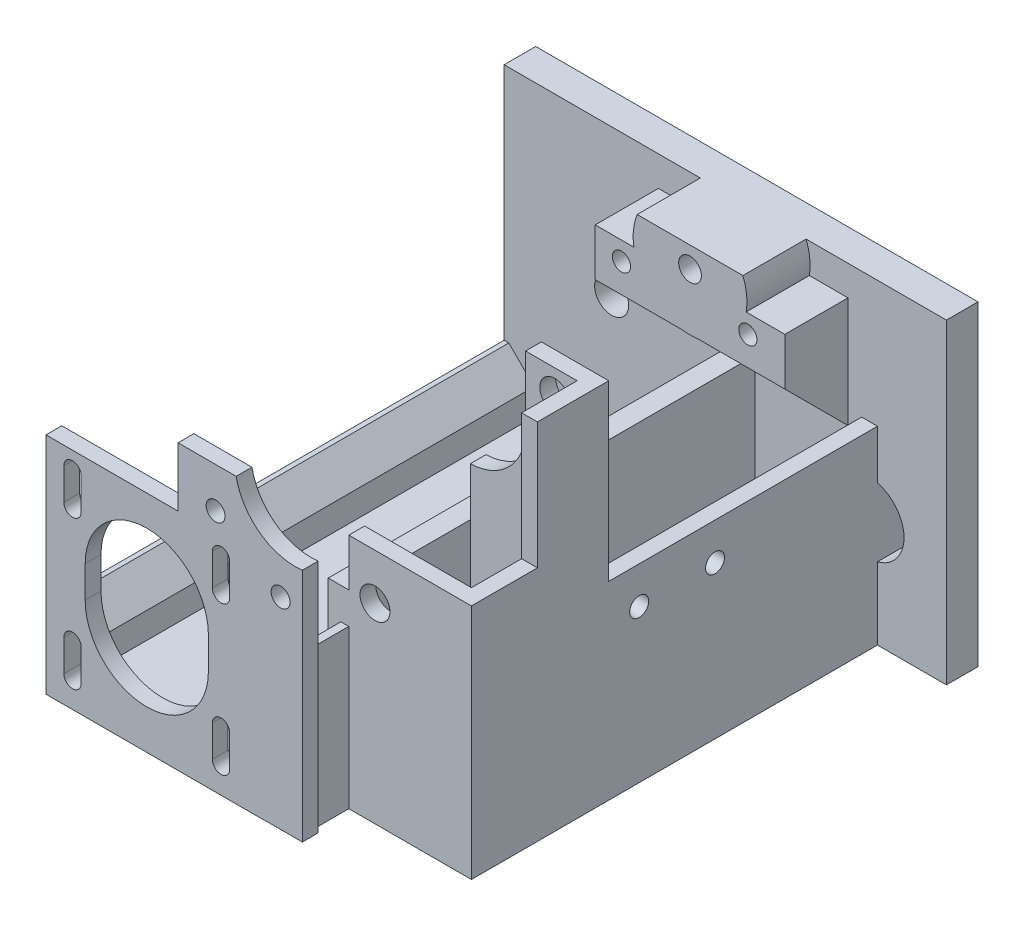
SolidWorks part; units mm, degrees
material "ABS"
ref_plane "Front Plane" through (0, 0, 0) normal (0, 0, 1) x (1, 0, 0)
ref_plane "Top Plane" through (0, 0, 0) normal (0, 1, 0) x (1, 0, 0)
ref_plane "Right Plane" through (0, 0, 0) normal (1, 0, 0) x (0, 0, -1)
sketch "Sketch1" plane through (0, 0, 0) normal (0, 0, 1) x (1, 0, 0)
  line L1 (-65.5446, 32.6733) -> (74.4554, 32.6733)
  line L2 (-65.5446, 32.6733) -> (-65.5446, -67.3267)
  line L3 (-65.5446, -67.3267) -> (74.4554, -67.3267)
  line L4 (74.4554, 32.6733) -> (74.4554, -67.3267)
  dimension "D1" = 100
  dimension "D2" = 140
extrude "Boss-Extrude1" add sketch "Sketch1" along normal blind 10
sketch "Sketch2" plane through (0, 0, 10) normal (0, 0, 1) x (1, 0, 0)
  line L0 (-65.5446, -67.3267) -> (-65.5446, -42.849)
  line L3 (-65.5446, -67.3267) -> (7.3151, -67.3267)
  line L5 (-65.5446, -67.3267) -> (74.4554, -67.3267) construction
  line L8 (-65.5446, 32.6733) -> (-65.5446, -67.3267) construction
  line L9 (-65.5446, -42.849) -> (-56.0483, -42.849)
  line L10 (-56.0483, -42.849) -> (-56.0483, -59.0904)
  line L11 (-56.0483, -59.0904) -> (7.3151, -59.0904)
  line L12 (7.3151, -59.0904) -> (7.3151, -7.3423)
  line L13 (7.3151, -7.3423) -> (13.8255, -7.3423)
  line L14 (13.8255, -7.3423) -> (13.8255, -67.3267)
  line L15 (13.8255, -67.3267) -> (7.3151, -67.3267)
extrude "Boss-Extrude2" add sketch "Sketch2" along normal blind 140
sketch "Sketch3" plane through (0, 0, 10) normal (0, 0, 1) x (1, 0, 0)
  line L1 (-16.6941, 23.1955) -> (43.3059, 23.1955)
  line L2 (-16.6941, 23.1955) -> (-16.6941, 8.1955)
  line L3 (-16.6941, 8.1955) -> (43.3059, 8.1955)
  line L4 (43.3059, 23.1955) -> (43.3059, 8.1955)
  dimension "D1" = 15
  dimension "D2" = 60
extrude "Boss-Extrude3" add sketch "Sketch3" along normal blind 20
sketch "Sketch4" plane through (0, 0, 10) normal (0, 0, 1) x (1, 0, 0)
  line L0 (43.3059, 8.1955) -> (43.3059, 23.1955) construction
  circle A0 centre (13.3059, 26.0432) radius 18
  dimension "D1" = 36
  dimension "D2" = 30
extrude "Boss-Extrude4" add sketch "Sketch4" along normal blind 20
sketch "Sketch6" plane through (0, 0, 30) normal (0, 0, 1) x (1, 0, 0)
  circle A0 centre (13.3059, 26.0432) radius 3.5973
  arc A1 (31.0792, 23.1955) -> (-4.4674, 23.1955) centre (13.3059, 26.0432) ccw construction
extrude "Cut-Extrude2" cut sketch "Sketch6" against normal blind 100
sketch "Sketch5" plane through (0, 0, 30) normal (0, 0, 1) x (1, 0, 0)
  line L0 (74.4554, 32.6733) -> (30.0404, 32.6733) construction
  line L1 (-13.303, 47.4) -> (34.4273, 47.4)
  line L2 (-13.303, 47.4) -> (-13.303, 32.6733)
  line L3 (-13.303, 32.6733) -> (34.4273, 32.6733)
  line L4 (34.4273, 47.4) -> (34.4273, 32.6733)
extrude "Cut-Extrude1" cut sketch "Sketch5" against normal blind 20
sketch "Sketch7" plane through (0, 0, 30) normal (0, 0, 1) x (1, 0, 0)
  circle A0 centre (-8.3949, 17.2978) radius 2.8779
extrude "Cut-Extrude3" cut sketch "Sketch7" against normal blind 100
pattern_linear "LPattern1" count 2 spacing 40 along (1, 0, 0) of "Cut-Extrude3"
sketch "Sketch9" plane through (0, 0, 150) normal (0, 0, 1) x (1, 0, 0)
  line L0 (-65.5446, 32.6733) -> (-65.5446, -42.849) construction
  line L1 (4.1877, 3.7072) -> (-65.5446, 3.7072)
  line L2 (4.1877, 3.7072) -> (4.1877, -67.3896)
  line L3 (4.1877, -67.3896) -> (-65.5446, -67.3896)
  line L4 (-65.5446, 3.7072) -> (-65.5446, -67.3896)
extrude "Boss-Extrude5" add sketch "Sketch9" along normal blind 5
chamfer "Chamfer1" distance 20 angle 45 2 edges at (29.4741, 8.1955, 10) (-2.8623, 8.1955, 10)
sketch "Sketch11" plane through (0, 0, 155) normal (0, 0, 1) x (1, 0, 0)
  line L0 (13.8255, -67.3267) -> (74.4554, -67.3267) construction
  line L1 (-23.7439, 22.4423) -> (15.6103, 22.4423)
  line L2 (-23.7439, 22.4423) -> (-23.7439, -67.3267)
  line L3 (-23.7439, -67.3267) -> (15.6103, -67.3267)
  line L4 (15.6103, 22.4423) -> (15.6103, -67.3267)
extrude "Boss-Extrude6" add sketch "Sketch11" against normal blind 5
sketch "Sketch12" plane through (0, 0, 155) normal (0, 0, 1) x (1, 0, 0)
  circle A0 centre (13.3059, 26.0432) radius 19
extrude "Cut-Extrude5" cut sketch "Sketch12" against normal blind 10
sketch "Sketch13" plane through (0, 0, 155) normal (0, 0, 1) x (1, 0, 0)
  circle A0 centre (-11.8599, 9.7129) radius 3
  circle A1 centre (8.7091, -3.6025) radius 3
  circle A2 centre (13.3059, 26.0432) radius 30 construction
  dimension "D1" = 6
  dimension "D2" = 6
extrude "Cut-Extrude6" cut sketch "Sketch13" against normal blind 10
fillet "Fillet2" radius 10 rebuild error yes
chamfer "Chamfer2" distance 8 angle 45 1 edges at (-56.0483, -42.849, 80)
sketch "Sketch14" plane through (0, 0, 10) normal (0, 0, 1) x (1, 0, 0)
  circle A0 centre (-31.5077, -13.6101) radius 5.3914
  circle A1 centre (49.8779, -33.6888) radius 11.1548
extrude "Cut-Extrude7" cut sketch "Sketch14" against normal blind 10
sketch "Sketch15" plane through (0, -67.3267, 0) normal (0, -1, 0) x (1, 0, 0)
  line L1 (4.5956, 95.0738) -> (52.6384, 95.0738)
  line L2 (4.5956, 95.0738) -> (4.5956, 138.5253)
  line L3 (4.5956, 138.5253) -> (52.6384, 138.5253)
  line L4 (52.6384, 95.0738) -> (52.6384, 138.5253)
extrude "Boss-Extrude7" add sketch "Sketch15" against normal blind 5
sketch "Sketch16" plane through (0, -62.3267, 0) normal (0, 1, 0) x (1, 0, 0)
  line L8 (13.8255, -133.5253) -> (13.8255, -138.5253)
  line L9 (13.8255, -138.5253) -> (13.8255, -95.0738) construction
  line L10 (13.8255, -138.5253) -> (52.6384, -138.5253)
  line L11 (52.6384, -138.5253) -> (52.6384, -116.7995)
  line L12 (52.6384, -95.0738) -> (52.6384, -138.5253) construction
  line L13 (52.6384, -116.7995) -> (47.6384, -116.7995)
  line L14 (47.6384, -116.7995) -> (47.6384, -133.5253)
  line L15 (47.6384, -133.5253) -> (13.8255, -133.5253)
  dimension "D1" = 5
  dimension "D2" = 5
extrude "Boss-Extrude8" add sketch "Sketch16" along normal blind 70
sketch "Sketch17" plane through (0, 7.6733, 0) normal (0, 1, 0) x (1, 0, 0)
  line L1 (28.8586, -179.0031) -> (38.4745, -179.0031)
  line L2 (28.8586, -179.0031) -> (28.8586, -197.9959)
  line L3 (28.8586, -197.9959) -> (38.4745, -197.9959)
  line L4 (38.4745, -179.0031) -> (38.4745, -197.9959)
extrude "Cut-Extrude8" cut sketch "Sketch17" against normal blind 20 rebuild error yes
sketch "Sketch18" plane through (0, 0, 138.5253) normal (0, 0, 1) x (1, 0, 0)
  circle A0 centre (22.1124, -6.8448) radius 4.75
  dimension "D1" = 9.5
extrude "Cut-Extrude9" cut sketch "Sketch18" against normal blind 20
sketch "Sketch19" plane through (0, -62.3267, 0) normal (0, 1, 0) x (1, 0, 0)
  line L0 (13.8199, -95.0738) -> (13.8199, -100.0738)
  line L3 (13.8199, -100.0738) -> (47.6384, -100.0738)
  line L6 (47.6384, -100.0738) -> (47.6384, -117.6475)
  line L7 (47.6384, -117.6475) -> (52.6384, -117.6475)
  line L8 (52.6384, -95.0738) -> (52.6384, -116.7995) construction
  line L9 (52.6384, -117.6475) -> (52.6384, -95.0738)
  line L10 (52.6384, -95.0738) -> (13.8199, -95.0738)
  dimension "D1" = 5
  dimension "D2" = 5
extrude "Boss-Extrude9" add sketch "Sketch19" along normal blind 110
sketch "Sketch20" plane through (0, 0, 100.0738) normal (0, 0, 1) x (1, 0, 0)
  line L0 (13.3059, 26.0432) -> (13.3059, 51.1413) construction
  line L1 (-4.7235, 26.0432) -> (-4.7235, 51.1413)
  line L2 (31.3354, 26.0432) -> (31.3354, 51.1413)
  arc A0 (-4.7235, 26.0432) -> (31.3354, 26.0432) centre (13.3059, 26.0432) ccw
  arc A1 (31.3354, 51.1413) -> (-4.7235, 51.1413) centre (13.3059, 51.1413) ccw
  point P3 (13.3059, 38.5923)
extrude "Cut-Extrude10" cut sketch "Sketch20" against normal blind 70
sketch "Sketch21" plane through (0, 0, 100.0738) normal (0, 0, 1) x (1, 0, 0)
  circle A0 centre (40.582, 40.031) radius 4.75
  dimension "D1" = 9.5
extrude "Cut-Extrude11" cut sketch "Sketch21" against normal blind 70
sketch "Sketch22" plane through (0, 0, 155) normal (0, 0, 1) x (1, 0, 0)
  line L0 (-57.1445, -58.9171) -> (-57.1445, -48.9171) construction
  line L1 (-59.8916, -58.9171) -> (-59.8916, -48.9171)
  line L2 (-54.3974, -58.9171) -> (-54.3974, -48.9171)
  line L3 (-33.6445, -35.4171) -> (-33.6445, -25.4171) construction
  line L4 (-53.1445, -35.4171) -> (-53.1445, -25.4171)
  line L5 (-14.1445, -35.4171) -> (-14.1445, -25.4171)
  line L6 (-10.1445, -58.9171) -> (-10.1445, -48.9171) construction
  line L7 (-12.8916, -58.9171) -> (-12.8916, -48.9171)
  line L8 (-7.3974, -58.9171) -> (-7.3974, -48.9171)
  line L9 (-10.1445, -11.9171) -> (-10.1445, -1.9171) construction
  line L10 (-12.8916, -11.9171) -> (-12.8916, -1.9171)
  line L11 (-7.3974, -11.9171) -> (-7.3974, -1.9171)
  line L12 (-57.1445, -11.9171) -> (-57.1445, -1.9171) construction
  line L13 (-59.8916, -11.9171) -> (-59.8916, -1.9171)
  line L14 (-54.3974, -11.9171) -> (-54.3974, -1.9171)
  arc A0 (-59.8916, -58.9171) -> (-54.3974, -58.9171) centre (-57.1445, -58.9171) ccw
  arc A1 (-54.3974, -48.9171) -> (-59.8916, -48.9171) centre (-57.1445, -48.9171) ccw
  arc A2 (-53.1445, -35.4171) -> (-14.1445, -35.4171) centre (-33.6445, -35.4171) ccw
  arc A3 (-14.1445, -25.4171) -> (-53.1445, -25.4171) centre (-33.6445, -25.4171) ccw
  arc A4 (-12.8916, -58.9171) -> (-7.3974, -58.9171) centre (-10.1445, -58.9171) ccw
  arc A5 (-7.3974, -48.9171) -> (-12.8916, -48.9171) centre (-10.1445, -48.9171) ccw
  arc A6 (-12.8916, -11.9171) -> (-7.3974, -11.9171) centre (-10.1445, -11.9171) ccw
  arc A7 (-7.3974, -1.9171) -> (-12.8916, -1.9171) centre (-10.1445, -1.9171) ccw
  arc A8 (-59.8916, -11.9171) -> (-54.3974, -11.9171) centre (-57.1445, -11.9171) ccw
  arc A9 (-54.3974, -1.9171) -> (-59.8916, -1.9171) centre (-57.1445, -1.9171) ccw
  point P2 (-57.1445, -53.9171)
  point P9 (-33.6445, -30.4171)
  point P16 (-10.1445, -53.9171)
  point P23 (-10.1445, -6.9171)
  point P30 (-57.1445, -6.9171)
  dimension "D5" = 19.5
  dimension "D1" = 10
  dimension "D2" = 10
  dimension "D3" = 23.5
  dimension "D4" = 23.5
extrude "Cut-Extrude12" cut sketch "Sketch22" against normal blind 10
sketch "Sketch23" plane through (7.3151, 0, 0) normal (-1, 0, 0) x (0, 0, 1)
  line L0 (150, 3.7072) -> (150, -42.849) construction
  line L1 (138.5253, -7.3423) -> (150, -7.3423)
  line L2 (138.5253, -7.3423) -> (138.5253, -17.3423)
  line L3 (138.5253, -17.3423) -> (150, -17.3423)
  line L4 (150, -7.3423) -> (150, -17.3423)
  dimension "D1" = 10
extrude "Cut-Extrude13" cut sketch "Sketch23" against normal blind 10
chamfer "Chamfer4" distance 4 angle 45 1 edges at (7.3151, -17.3423, 144.2627)
sketch "Sketch24" plane through (0, -67.3267, 0) normal (0, -1, 0) x (1, 0, 0)
  line L0 (-65.5446, 0) -> (74.4554, 0) construction
  line L1 (52.6384, 0) -> (47.6384, 0)
  line L2 (52.6384, 0) -> (52.6384, 106.4381)
  line L3 (52.6384, 106.4381) -> (47.6384, 106.4381)
  line L4 (47.6384, 0) -> (47.6384, 106.4381)
  line L6 (52.6384, 95.0738) -> (52.6384, 138.5253) construction
  dimension "D1" = 5
extrude "Boss-Extrude10" add sketch "Sketch24" against normal blind 60
sketch "Sketch25" plane through (52.6384, 0, 0) normal (1, 0, 0) x (0, 0, -1)
  circle A0 centre (-85.4201, -19.0527) radius 3
  point P2 (-85.4201, -19.0527)
extrude "Cut-Extrude14" cut sketch "Sketch25" against normal blind 20
pattern_linear "LPattern2" count 2 spacing 24 along (0, 0, -1) of "Cut-Extrude14"
